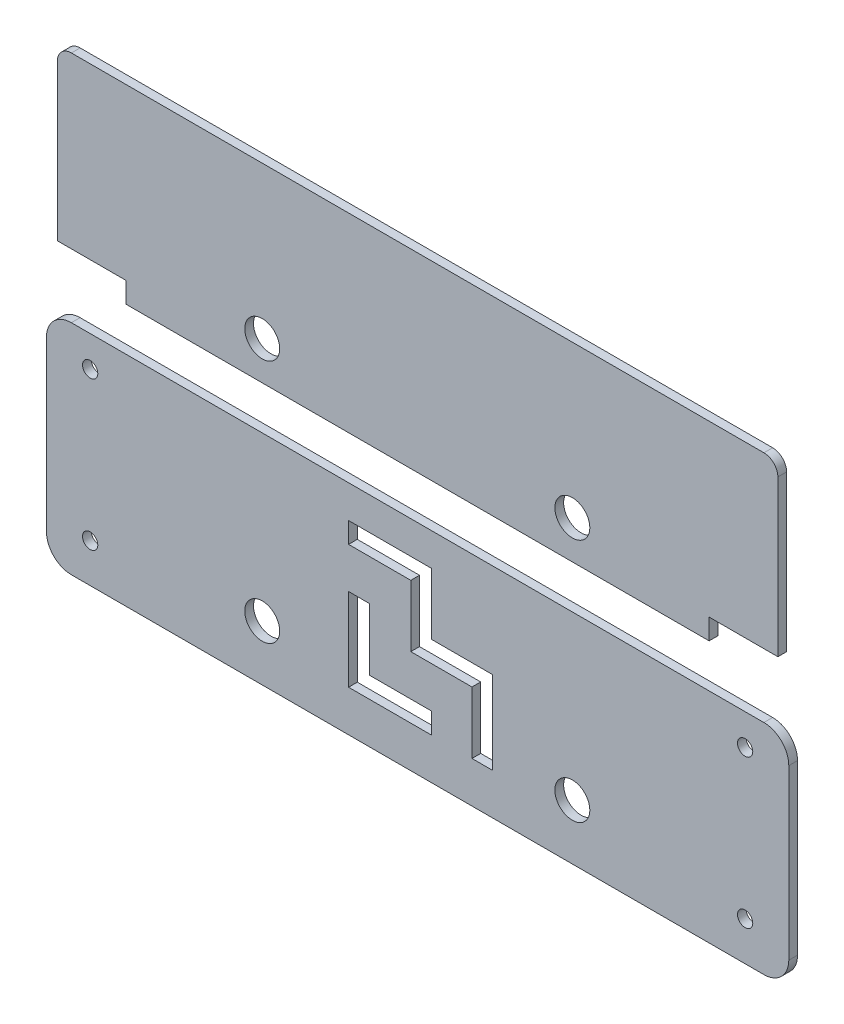
SolidWorks part; units mm, degrees
ref_plane "Front" through (0, 0, 0) normal (0, 0, 1) x (1, 0, 0)
ref_plane "Top" through (0, 0, 0) normal (0, 1, 0) x (1, 0, 0)
ref_plane "Right" through (0, 0, 0) normal (1, 0, 0) x (0, 0, -1)
sketch "Sketch1" plane through (0, 0, 0) normal (0, 0, 1) x (1, 0, 0)
  line L0 (-52.6295, -31.75) -> (-37.7705, -31.75)
  line L1 (37.5705, -31.75) -> (52.4295, -31.75)
  line L2 (-107.95, 24.511) -> (-107.95, -24.511)
  line L3 (-100.711, -31.75) -> (-52.6295, -31.75)
  line L4 (-37.7705, -31.75) -> (37.5705, -31.75)
  line L5 (52.4295, -31.75) -> (100.711, -31.75)
  line L6 (107.95, -24.511) -> (107.95, 24.511)
  line L7 (100.711, 31.75) -> (-100.711, 31.75)
  line L24 (100.711, 99.695) -> (-100.711, 99.695)
  line L25 (-104.775, 95.631) -> (-104.775, 50.345)
  line L31 (104.775, 50.345) -> (104.775, 95.631)
  line L32 (107.95, 46.609) -> (107.95, 95.631) [skipped]
  line L33 (84.775, 44.345) -> (-84.775, 44.345)
  line L34 (100.711, 102.87) -> (-100.711, 102.87) [skipped]
  line L35 (84.775, 44.345) -> (84.775, 50.345)
  line L36 (52.4295, 39.37) -> (100.711, 39.37) [skipped]
  line L37 (84.775, 50.345) -> (104.775, 50.345)
  line L38 (37.5705, 39.37) -> (52.4295, 39.37) [skipped]
  line L40 (-37.7705, 39.37) -> (37.5705, 39.37) [skipped]
  line L41 (0, 99.695) -> (0, 44.345) construction
  line L42 (-52.6295, 39.37) -> (-37.7705, 39.37) [skipped]
  line L43 (-84.775, 50.345) -> (-104.775, 50.345)
  line L44 (-100.711, 39.37) -> (-52.6295, 39.37) [skipped]
  line L45 (-84.775, 44.345) -> (-84.775, 50.345)
  line L46 (-107.95, 95.631) -> (-107.95, 46.609) [skipped]
  circle A0 centre (-45.2, -15.6502) radius 5.08
  circle A1 centre (45, -15.6502) radius 5.08
  arc A2 (-100.711, 31.75) -> (-107.95, 24.511) centre (-100.711, 24.511) ccw
  arc A3 (-107.95, -24.511) -> (-100.711, -31.75) centre (-100.711, -24.511) ccw
  arc A4 (100.711, -31.75) -> (107.95, -24.511) centre (100.711, -24.511) ccw
  arc A5 (107.95, 24.511) -> (100.711, 31.75) centre (100.711, 24.511) ccw
  circle A10 centre (-45.2, 55.4698) radius 5.08
  circle A11 centre (45, 55.4698) radius 5.08
  arc A18 (-100.711, 99.695) -> (-104.775, 95.631) centre (-100.711, 95.631) ccw
  arc A21 (104.775, 95.631) -> (100.711, 99.695) centre (100.711, 95.631) ccw
  arc A24 (107.95, 95.631) -> (100.711, 102.87) centre (100.711, 95.631) ccw [skipped]
  circle A25 centre (66.273, 2.3) radius 1.905 construction
  arc A26 (100.711, 39.37) -> (107.95, 46.609) centre (100.711, 46.609) ccw [skipped]
  arc A28 (-107.95, 46.609) -> (-100.711, 39.37) centre (-100.711, 46.609) ccw [skipped]
  circle A29 centre (35.023, 2.3) radius 1.905 construction
  arc A30 (-100.711, 102.87) -> (-107.95, 95.631) centre (-100.711, 95.631) ccw [skipped]
  circle A32 centre (50.648, 2.3) radius 12.065 construction
  circle A34 centre (12.5, 2.3) radius 9.25 construction
  dimension "D3" = 2
extrude "Boss-Extrude1" add sketch "Sketch1" along normal blind 2.54
sketch "Sketch2" plane through (0, 0, 2.54) normal (0, 0, 1) x (1, 0, 0)
  line L0 (-20.0864, 22.2366) -> (3.9841, 22.2366)
  line L1 (3.9841, 22.2366) -> (3.9841, 4.3544)
  line L2 (3.9841, 4.3544) -> (21.8236, 4.3544)
  line L3 (21.8236, 4.3544) -> (21.8236, -19.7588)
  line L4 (21.8236, -19.7588) -> (15.806, -19.7588)
  line L5 (15.806, -19.7588) -> (15.806, -1.7486)
  line L6 (15.806, -1.7486) -> (-1.9908, -1.7486)
  line L7 (-1.9908, -1.7486) -> (-1.9908, 16.2189)
  line L8 (-1.9908, 16.2189) -> (-20.0864, 16.2189)
  line L9 (-20.0864, 16.2189) -> (-20.0864, 22.2366)
  line L10 (-20.0864, 4.3544) -> (-14.0261, 4.3544)
  line L11 (-14.0261, 4.3544) -> (-14.0261, -13.6985)
  line L12 (-14.0261, -13.6985) -> (3.9841, -13.6985)
  line L13 (3.9841, -13.6985) -> (3.9841, -19.7588)
  line L14 (3.9841, -19.7588) -> (-20.0864, -19.7588)
  line L15 (-20.0864, -19.7588) -> (-20.0864, 4.3544)
extrude "Cut-Extrude1" cut sketch "Sketch2" against normal through all
sketch "Sketch3" [suppressed] plane through (0, 0, 2.54) normal (0, 0, 1) x (1, 0, 0)
  circle A0 centre (-45.2, 55.4698) radius 5.08 construction
  circle A1 centre (-45.2, 55.4698) radius 5.08
  circle A2 centre (45, 55.4698) radius 5.08 construction
  circle A3 centre (45, 55.4698) radius 5.08
extrude "Boss-Extrude2" [suppressed] add sketch "Sketch3" against normal through all
sketch "Sketch5" [suppressed] plane through (0, 0, 2.54) normal (0, 0, 1) x (1, 0, 0)
  line L0 (3.9841, -19.7588) -> (3.9841, -13.6985) construction
  line L1 (-20.0864, -19.7588) -> (3.9841, -19.7588) construction
  line L2 (-20.0864, 4.3544) -> (-20.0864, -19.7588) construction
  line L3 (-14.0261, 4.3544) -> (-20.0864, 4.3544) construction
  line L4 (-14.0261, -13.6985) -> (-14.0261, 4.3544) construction
  line L5 (3.9841, -13.6985) -> (-14.0261, -13.6985) construction
  line L6 (3.9841, -19.7588) -> (3.9841, -13.6985)
  line L7 (-20.0864, -19.7588) -> (3.9841, -19.7588)
  line L8 (-20.0864, 4.3544) -> (-20.0864, -19.7588)
  line L9 (-14.0261, 4.3544) -> (-20.0864, 4.3544)
  line L10 (-14.0261, -13.6985) -> (-14.0261, 4.3544)
  line L11 (3.9841, -13.6985) -> (-14.0261, -13.6985)
  line L12 (-1.9908, -1.7486) -> (15.806, -1.7486) construction
  line L13 (-1.9908, 16.2189) -> (-1.9908, -1.7486) construction
  line L14 (-20.0864, 16.2189) -> (-1.9908, 16.2189) construction
  line L15 (-20.0864, 22.2366) -> (-20.0864, 16.2189) construction
  line L16 (3.9841, 22.2366) -> (-20.0864, 22.2366) construction
  line L17 (3.9841, 4.3544) -> (3.9841, 22.2366) construction
  line L18 (21.8236, 4.3544) -> (3.9841, 4.3544) construction
  line L19 (21.8236, -19.7588) -> (21.8236, 4.3544) construction
  line L20 (15.806, -19.7588) -> (21.8236, -19.7588) construction
  line L21 (15.806, -1.7486) -> (15.806, -19.7588) construction
  line L22 (-1.9908, -1.7486) -> (15.806, -1.7486)
  line L23 (-1.9908, 16.2189) -> (-1.9908, -1.7486)
  line L24 (-20.0864, 16.2189) -> (-1.9908, 16.2189)
  line L25 (-20.0864, 22.2366) -> (-20.0864, 16.2189)
  line L26 (3.9841, 22.2366) -> (-20.0864, 22.2366)
  line L27 (3.9841, 4.3544) -> (3.9841, 22.2366)
  line L28 (21.8236, 4.3544) -> (3.9841, 4.3544)
  line L29 (21.8236, -19.7588) -> (21.8236, 4.3544)
  line L30 (15.806, -19.7588) -> (21.8236, -19.7588)
  line L31 (15.806, -1.7486) -> (15.806, -19.7588)
  circle A0 centre (-45.2, -15.6502) radius 5.08 construction
  circle A1 centre (-45.2, -15.6502) radius 5.08
  circle A2 centre (45, -15.6502) radius 5.08 construction
  circle A3 centre (45, -15.6502) radius 5.08
extrude "Boss-Extrude3" [suppressed] add sketch "Sketch5" against normal through all
sketch "Sketch6" [suppressed] plane through (0, 0, 2.54) normal (0, 0, 1) x (1, 0, 0)
  circle A0 centre (12.5, 2.3) radius 9.25 construction
  circle A1 centre (12.5, 2.3) radius 9.25
  circle A2 centre (35.023, 2.3) radius 1.905 construction
  circle A3 centre (35.023, 2.3) radius 1.905
  circle A4 centre (50.648, 2.3) radius 12.065 construction
  circle A5 centre (50.648, 2.3) radius 12.065
  circle A6 centre (66.273, 2.3) radius 1.905 construction
  circle A7 centre (66.273, 2.3) radius 1.905
extrude "Cut-Extrude2" [suppressed] cut sketch "Sketch6" against normal through all
sketch "Sketch7" [suppressed] plane through (0, 0, 0) normal (0, 0, -1) x (-1, 0, 0)
  line L1 (-74.2733, 90.9286) -> (5.6813, 90.9286)
  line L2 (-74.2733, 90.9286) -> (-74.2733, 56.2734)
  line L3 (-74.2733, 56.2734) -> (5.6813, 56.2734)
  line L4 (5.6813, 90.9286) -> (5.6813, 56.2734)
extrude "Cut-Extrude3" [suppressed] cut sketch "Sketch7" against normal through all
sketch "Sketch8" plane through (0, 0, 2.54) normal (0, 0, 1) x (1, 0, 0)
  line L0 (0, 31.75) -> (0, 1.16) construction
  line L1 (95.25, -20.43) -> (-95.25, -20.43) construction
  line L2 (95.25, -20.43) -> (95.25, 22.75) construction
  line L3 (95.25, 22.75) -> (-95.25, 22.75) construction
  line L4 (-95.25, -20.43) -> (-95.25, 22.75) construction
  line L5 (95.25, -20.43) -> (-95.25, 22.75) construction
  line L6 (95.25, 22.75) -> (-95.25, -20.43) construction
  line L7 (100.711, 31.75) -> (-100.711, 31.75) construction
  circle A0 centre (-95.25, 22.75) radius 2.2225
  circle A1 centre (-95.25, -20.43) radius 2.2225
  circle A2 centre (95.25, -20.43) radius 2.2225
  circle A3 centre (95.25, 22.75) radius 2.2225
  dimension "D1" = 4.445
  dimension "D2" = 43.18
  dimension "D3" = 190.5
  dimension "D4" = 9
extrude "Cut-Extrude4" cut sketch "Sketch8" against normal through all
sketch "Sketch9" [suppressed] plane through (0, 0, 2.54) normal (0, 0, 1) x (1, 0, 0)
  line L0 (-104.775, 50.345) -> (-84.775, 50.345)
  line L1 (-84.775, 50.345) -> (-84.775, 44.345)
  line L2 (-84.775, 44.345) -> (-104.775, 44.345)
  line L3 (-104.775, 44.345) -> (-104.775, 50.345)
  line L4 (84.775, 50.345) -> (104.775, 50.345)
  line L5 (104.775, 50.345) -> (104.775, 44.345)
  line L6 (104.775, 44.345) -> (84.775, 44.345)
  line L7 (84.775, 50.345) -> (84.775, 44.345)
extrude "Boss-Extrude4" [suppressed] add sketch "Sketch9" against normal up to surface (2.54 mm away) up to face at (0, 68.2405, 0)
fillet "Fillet1" [suppressed] radius 2
sketch "Sketch10" [suppressed] plane through (0, 0, 2.54) normal (0, 0, 1) x (1, 0, 0)
  circle A1 centre (95.25, 93.87) radius 2.2225
  circle A2 centre (95.25, 93.87) radius 2.2225
  circle A3 centre (95.25, 50.69) radius 2.2225
  circle A4 centre (95.25, 50.69) radius 2.2225
  circle A5 centre (-95.25, 50.69) radius 2.2225
  circle A6 centre (-95.25, 50.69) radius 2.2225
  circle A7 centre (-95.25, 93.87) radius 2.2225
  circle A8 centre (-95.25, 93.87) radius 2.2225
  dimension "D1" = 0
  dimension "D2" = 0
  dimension "D3" = 0
  dimension "D4" = 0
extrude "Cut-Extrude5" [suppressed] cut sketch "Sketch10" against normal through all
sketch "Sketch12" [suppressed] plane through (0, 0, 0) normal (0, 0, -1) x (-1, 0, 0)
  line L1 (104.775, 50.345) -> (84.775, 50.345)
  line L2 (104.775, 50.345) -> (104.775, 44.345)
  line L3 (104.775, 44.345) -> (84.775, 44.345)
  line L4 (84.775, 50.345) -> (84.775, 44.345)
  line L5 (-104.775, 50.345) -> (-84.775, 50.345)
  line L6 (-104.775, 50.345) -> (-104.775, 44.345)
  line L7 (-104.775, 44.345) -> (-84.775, 44.345)
  line L8 (-84.775, 50.345) -> (-84.775, 44.345)
extrude "Boss-Extrude5" [suppressed] add sketch "Sketch12" against normal up to surface (2.54 mm away) up to face at (-40.12, 55.4698, 2.54)
fillet "Fillet2" [suppressed] radius 2.5
sketch "Sketch11" [suppressed] plane through (0, 0, 2.54) normal (0, 0, 1) x (1, 0, 0)
  circle A1 centre (95.25, 93.87) radius 2.2225
  circle A2 centre (95.25, 93.87) radius 2.2225
  circle A3 centre (95.25, 50.69) radius 2.2225
  circle A4 centre (95.25, 50.69) radius 2.2225
  circle A5 centre (-95.25, 50.69) radius 2.2225
  circle A6 centre (-95.25, 50.69) radius 2.2225
  circle A7 centre (-95.25, 93.87) radius 2.2225
  circle A8 centre (-95.25, 93.87) radius 2.2225
  dimension "D1" = 0
  dimension "D2" = 0
  dimension "D3" = 0
  dimension "D4" = 0
extrude "Cut-Extrude6" [suppressed] cut sketch "Sketch11" against normal through all
sketch "Sketch13" [suppressed] plane through (0, 0, 2.54) normal (0, 0, 1) x (1, 0, 0)
  circle A1 centre (-95.25, 22.75) radius 2.2225
  circle A2 centre (-95.25, 22.75) radius 2.2225
  circle A3 centre (-95.25, -20.43) radius 2.2225
  circle A4 centre (-95.25, -20.43) radius 2.2225
  circle A5 centre (95.25, -20.43) radius 2.2225
  circle A6 centre (95.25, -20.43) radius 2.2225
  circle A7 centre (95.25, 22.75) radius 2.2225
  circle A8 centre (95.25, 22.75) radius 2.2225
  dimension "D1" = 0
  dimension "D2" = 0
  dimension "D3" = 0
  dimension "D4" = 0
extrude "Cut-Extrude7" [suppressed] cut sketch "Sketch13" against normal through all
